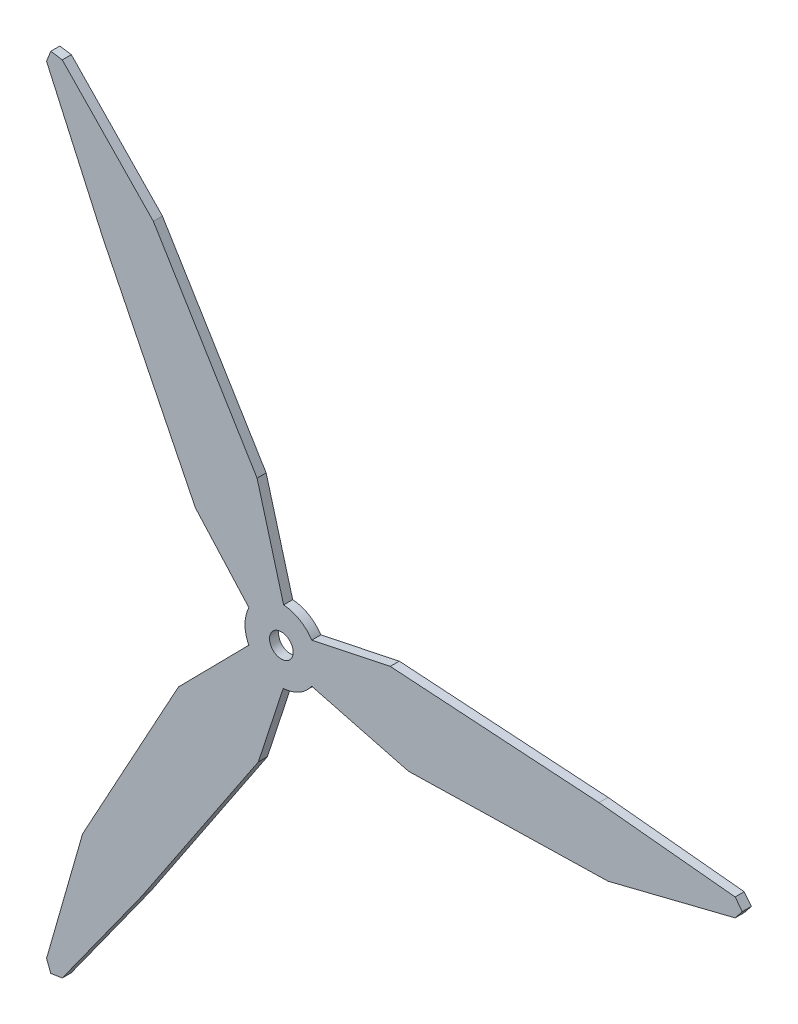
SolidWorks part; units mm, degrees
ref_plane "前视基准面" through (0, 0, 0) normal (0, 0, 1) x (1, 0, 0)
ref_plane "上视基准面" through (0, 0, 0) normal (0, 1, 0) x (1, 0, 0)
ref_plane "右视基准面" through (0, 0, 0) normal (1, 0, 0) x (0, 0, -1)
other "Configuration Table"
sketch "草图1" plane through (0, 0, 0) normal (0, 0, 1) x (1, 0, 0)
  circle A0 centre (0, 0) radius 8
  circle A1 centre (0, 0) radius 2.6
extrude "桨毂" add sketch "草图1" along normal blind 2
sketch "草图2" plane through (0, 0, 0) normal (0, 0, 1) x (1, 0, 0)
  line L16 (5, -4) -> (28, -10)
  line L17 (28, -10) -> (72, -9)
  line L18 (72, -9) -> (100, -2)
  line L19 (100, -2) -> (101.6, 0)
  line L20 (101.6, 0) -> (100, 2)
  line L21 (100, 2) -> (70, 5)
  line L22 (70, 5) -> (24, 8)
  line L23 (24, 8) -> (5, 4)
  line L24 (5, 4) -> (5, -4)
  line L25 (0.9641, 6.3301) -> (-5.3397, 29.2487)
  line L26 (-5.3397, 29.2487) -> (-28.2058, 66.8538)
  line L27 (-28.2058, 66.8538) -> (-48.2679, 87.6025)
  line L28 (-48.2679, 87.6025) -> (-50.8, 87.9882)
  line L29 (-50.8, 87.9882) -> (-51.7321, 85.6025)
  line L30 (-51.7321, 85.6025) -> (-39.3301, 58.1218)
  line L31 (-39.3301, 58.1218) -> (-18.9282, 16.7846)
  line L32 (-18.9282, 16.7846) -> (-5.9641, 2.3301)
  line L33 (-5.9641, 2.3301) -> (0.9641, 6.3301)
  line L34 (-5.9641, -2.3301) -> (-22.6603, -19.2487)
  line L35 (-22.6603, -19.2487) -> (-43.7942, -57.8538)
  line L36 (-43.7942, -57.8538) -> (-51.7321, -85.6025)
  line L37 (-51.7321, -85.6025) -> (-50.8, -87.9882)
  line L38 (-50.8, -87.9882) -> (-48.2679, -87.6025)
  line L39 (-48.2679, -87.6025) -> (-30.6699, -63.1218)
  line L40 (-30.6699, -63.1218) -> (-5.0718, -24.7846)
  line L41 (-5.0718, -24.7846) -> (0.9641, -6.3301)
  line L42 (0.9641, -6.3301) -> (-5.9641, -2.3301)
extrude "8寸三叶桨轮廓_120度均布" add sketch "草图2" along normal blind 2
ref_axis "桨叶旋转轴_Z" through (0, 0, -0.1) along (0, 0, 1)
